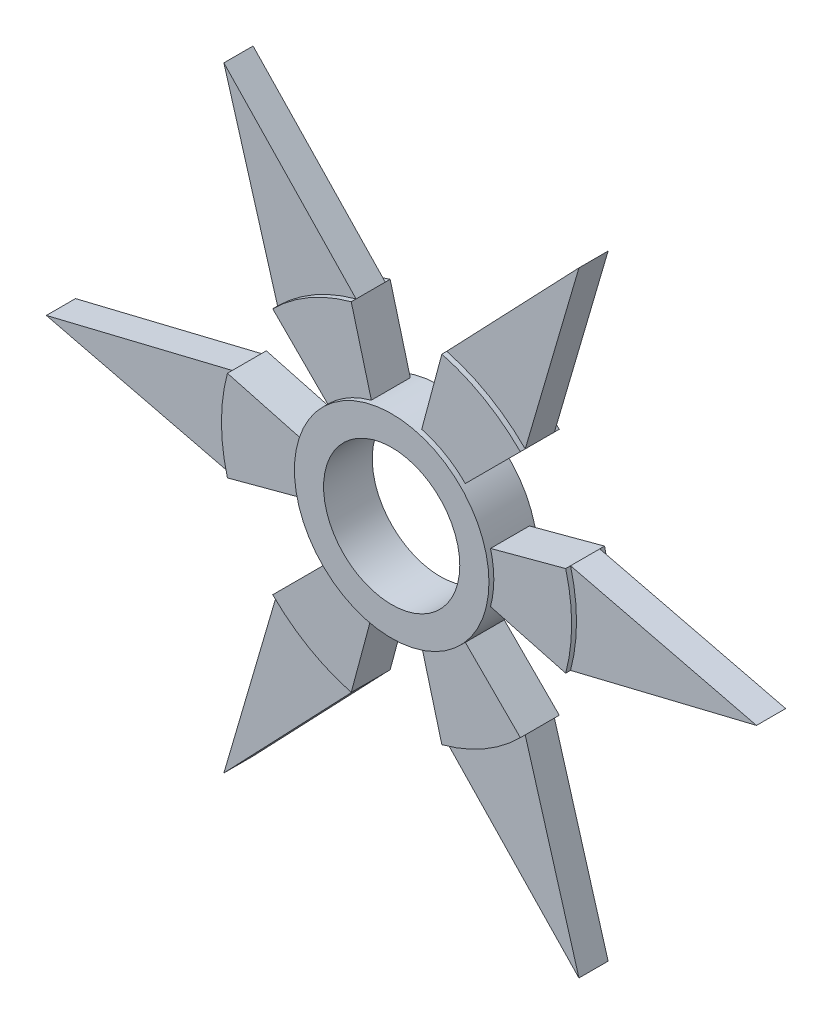
SolidWorks part; units mm, degrees
ref_plane "Front Plane" through (0, 0, 0) normal (0, 0, 1) x (1, 0, 0)
ref_plane "Top Plane" through (0, 0, 0) normal (0, 1, 0) x (1, 0, 0)
ref_plane "Right Plane" through (0, 0, 0) normal (1, 0, 0) x (0, 0, -1)
sketch "Sketch1" plane through (0, 0, 0) normal (0, 0, 1) x (1, 0, 0)
  line L0 (0, 0) -> (0, 28767.6328) construction
  line L1 (0, 0) -> (28767.6328, 0) construction
  line L2 (19.3185, 5.1764) -> (34.7733, 9.3175)
  line L3 (34.7733, 9.3175) -> (73, 0)
  line L4 (34.7733, -9.3175) -> (73, 0)
  line L5 (19.3185, -5.1764) -> (34.7733, -9.3175)
  line L6 (19.3185, 5.1764) -> (0, 0) construction
  line L7 (0, 0) -> (19.3185, -5.1764) construction
  line L8 (9.3175, -34.7733) -> (36.5, -63.2199)
  line L9 (25.4558, -25.4558) -> (36.5, -63.2199)
  line L10 (14.1421, -14.1421) -> (25.4558, -25.4558)
  line L11 (5.1764, -19.3185) -> (9.3175, -34.7733)
  line L12 (-25.4558, -25.4558) -> (-36.5, -63.2199)
  line L13 (-9.3175, -34.7733) -> (-36.5, -63.2199)
  line L14 (-5.1764, -19.3185) -> (-9.3175, -34.7733)
  line L15 (-14.1421, -14.1421) -> (-25.4558, -25.4558)
  line L16 (-34.7733, 9.3175) -> (-73, 0)
  line L17 (-34.7733, -9.3175) -> (-73, 0)
  line L18 (-19.3185, -5.1764) -> (-34.7733, -9.3175)
  line L19 (-19.3185, 5.1764) -> (-34.7733, 9.3175)
  line L20 (-9.3175, 34.7733) -> (-36.5, 63.2199)
  line L21 (-25.4558, 25.4558) -> (-36.5, 63.2199)
  line L22 (-14.1421, 14.1421) -> (-25.4558, 25.4558)
  line L23 (-5.1764, 19.3185) -> (-9.3175, 34.7733)
  line L24 (25.4558, 25.4558) -> (36.5, 63.2199)
  line L25 (9.3175, 34.7733) -> (36.5, 63.2199)
  line L26 (5.1764, 19.3185) -> (9.3175, 34.7733)
  line L27 (14.1421, 14.1421) -> (25.4558, 25.4558)
  circle A0 centre (0, 0) radius 20
  circle A1 centre (0, 0) radius 14
  arc A2 (-9.3175, 34.7733) -> (-25.4558, 25.4558) centre (0, 0) ccw
  circle A3 centre (0, 0) radius 73 construction
  arc A4 (-34.7733, 9.3175) -> (-34.7733, -9.3175) centre (0, 0) ccw
  arc A5 (-25.4558, -25.4558) -> (-9.3175, -34.7733) centre (0, 0) ccw
  arc A6 (9.3175, -34.7733) -> (25.4558, -25.4558) centre (0, 0) ccw
  arc A7 (34.7733, -9.3175) -> (34.7733, 9.3175) centre (0, 0) ccw
  arc A8 (25.4558, 25.4558) -> (9.3175, 34.7733) centre (0, 0) ccw
  point P43 (0, 0)
  dimension "D1" = 28
  dimension "D2" = 40
  dimension "D3" = 72
  dimension "D5" = 146
  dimension "D6" = 6
  dimension "D4" = 15
extrude "Boss-Extrude1" add sketch "Sketch1" along normal mid plane 10 contours A0 A1 region at (19.2681, 2.5367, 0)
extrude "Boss-Extrude2" add sketch "Sketch1<3>" along normal mid plane 8 contours L23 A2 L22 A0 | L27 A8 L26 A0 | L5 A7 L2 A0 | L11 A6 L10 A0 | L15 A5 L14 A0 | L19 A4 L18 A0 region at (28.4345, 0, 0) region at (14.2172, 24.625, 0) region at (14.2172, -24.625, 0) region at (-14.2172, 24.625, 0) region at (-14.2172, -24.625, 0) region at (-28.4345, 0, 0)
sketch "Sketch1<3>" plane through (0, 0, 0) normal (0, 0, 1) x (1, 0, 0) same geometry as "Sketch1"
extrude "Boss-Extrude3" add sketch "Sketch1<4>" along normal mid plane 6 contours A2 L20 L21 | A8 L24 L25 | A7 L4 L3 | A6 L8 L9 | A5 L12 L13 | A4 L16 L17 region at (48.0651, 0, 0) region at (24.0326, 41.6256, 0) region at (24.0326, -41.6256, 0) region at (-24.0326, 41.6256, 0) region at (-24.0326, -41.6256, 0) region at (-48.0651, 0, 0)
sketch "Sketch1<4>" plane through (0, 0, 0) normal (0, 0, 1) x (1, 0, 0) same geometry as "Sketch1"
